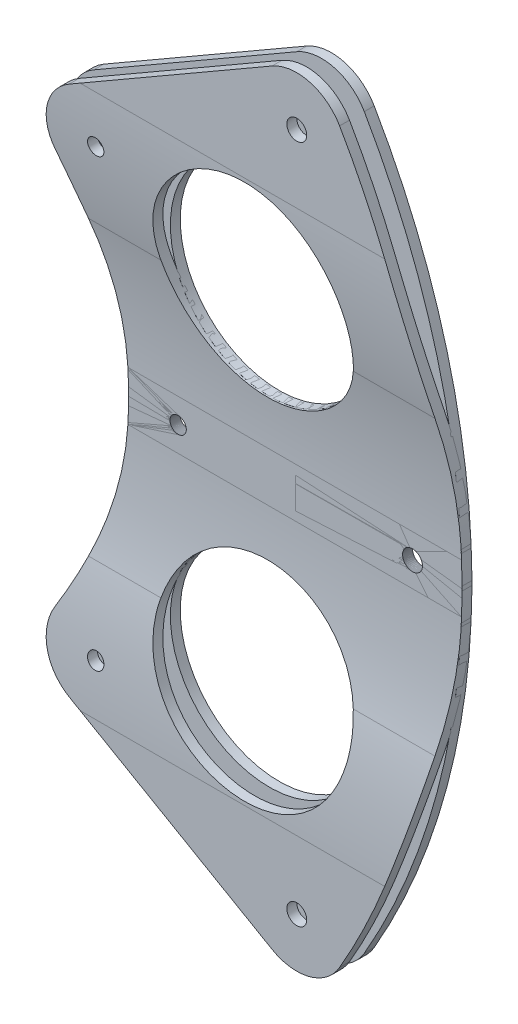
SolidWorks part; units mm, degrees
ref_plane "Front Plane" through (0, 0, 0) normal (0, 0, 1) x (1, 0, 0)
ref_plane "Top Plane" through (0, 0, 0) normal (0, 1, 0) x (1, 0, 0)
ref_plane "Right Plane" through (0, 0, 0) normal (1, 0, 0) x (0, 0, -1)
sketch "Sketch1" plane through (0, 0, 0) normal (0, 0, 1) x (1, 0, 0)
  line L0 (0, 0) -> (174.498, 0) construction
  line L1 (151.1197, 87.249) -> (0, 0) construction
  line L2 (0, 0) -> (151.1197, -87.249) construction
  line L3 (174.498, 0) -> (151.1197, 87.249) construction
  line L4 (174.498, 0) -> (151.1197, -87.249) construction
  line L5 (155.3947, 104.3819) -> (80.9481, 61.4001)
  line L6 (80.9481, -61.4001) -> (155.3947, -104.3819)
  line L7 (144.7697, 98.2475) -> (-25.4, 0) construction
  line L8 (-25.4, 0) -> (144.7697, -98.2475) construction
  circle A0 centre (0, 0) radius 88.9 construction
  circle A1 centre (0, 0) radius 114.3 construction
  circle A2 centre (0, 0) radius 174.498 construction
  circle A3 centre (174.498, 0) radius 2.5527
  circle A4 centre (151.1197, 87.249) radius 2.5527
  circle A5 centre (151.1197, -87.249) radius 2.5527
  circle A6 centre (98.9867, 57.15) radius 2.0955
  circle A8 centre (114.3, 0) radius 2.0955
  circle A9 centre (98.9867, -57.15) radius 2.0955
  arc A10 (155.3947, -104.3819) -> (155.3947, 104.3819) centre (0, 0) ccw
  arc A11 (80.9481, -61.4001) -> (80.9481, 61.4001) centre (0, 0) ccw
  circle A12 centre (0, 0) radius 101.6 construction
  circle A13 centre (0, 0) radius 187.198 construction
  dimension "D1" = 177.8
  dimension "D3" = 348.996
  dimension "D5" = 5.1054
  dimension "D6" = 4.191
  dimension "D4" = 30
  dimension "D2" = 25.4
  dimension "D7" = 12.7
  dimension "D8" = 12.7
extrude "Boss-Extrude1" add sketch "Sketch1" along normal blind 2.54
sketch "Sketch2" plane through (0, 0, 2.54) normal (0, 0, 1) x (1, 0, 0)
  line L2 (114.3, 0) -> (174.498, 0) construction
  line L3 (137.699, -43.4749) -> (137.699, 43.4749) construction
  line L4 (144.399, 0) -> (137.699, 43.4749) construction
  line L5 (137.699, 43.4749) -> (118.1714, 82.891) construction
  line L6 (155.3947, 104.3819) -> (80.9481, 61.4001) construction
  circle A0 centre (0, 0) radius 144.399 construction
  circle A1 centre (114.3, 0) radius 2.0955 construction
  circle A2 centre (137.699, 43.4749) radius 25.4
  circle A3 centre (137.699, -43.4749) radius 25.4
  point P3 (144.399, 0)
  point P16 (137.699, 0)
  dimension "D1" = 50.8
extrude "Cut-Extrude1" cut sketch "Sketch2" against normal through all both and the other way through all
sketch "Sketch3" plane through (0, 0, 0) normal (1, 0, 0) x (0, 0, -1)
  line L0 (-6.35, 87.249) -> (0, 87.249) construction
  line L1 (-6.35, -87.249) -> (0, -87.249) construction
  line L3 (-86.0519, 0) -> (0, 0) construction
  line L4 (0, 6.35) -> (0, -6.35)
  line L5 (-6.35, -104.7115) -> (-6.35, -69.7865)
  line L6 (-6.35, 104.7115) -> (-6.35, 69.7865)
  line L7 (-8.89, -104.7115) -> (-8.89, -69.7865)
  line L8 (-2.54, 6.35) -> (-2.54, -6.35)
  line L9 (-8.89, 104.7115) -> (-8.89, 69.7865)
  line L10 (-8.89, -104.7115) -> (-6.35, -104.7115)
  line L11 (-6.35, 104.7115) -> (-8.89, 104.7115)
  arc A0 (0, -6.35) -> (-3.175, -38.0683) centre (-160.0202, -6.35) cw
  arc A1 (-6.35, -69.7865) -> (-3.175, -38.0683) centre (153.6702, -69.7865) cw
  arc A2 (0, 6.35) -> (-3.175, 38.0683) centre (-160.0202, 6.35) ccw
  arc A3 (-3.175, 38.0683) -> (-6.35, 69.7865) centre (153.6702, 69.7865) cw
  arc A4 (-8.89, -69.7865) -> (-5.6646, -37.5648) centre (153.6702, -69.7865) cw
  arc A5 (-2.54, -6.35) -> (-5.6646, -37.5648) centre (-160.0202, -6.35) cw
  arc A6 (-2.54, 6.35) -> (-5.6646, 37.5648) centre (-160.0202, 6.35) ccw
  arc A7 (-5.6646, 37.5648) -> (-8.89, 69.7865) centre (153.6702, 69.7865) cw
  dimension "D1" = 6.35
  dimension "D2" = 34.925
  dimension "D3" = 12.7
  dimension "D4" = 2.54
extrude "Boss-Extrude2" add sketch "Sketch3" along normal blind 276.098 separate body contours L7 A4 A5 L8 A6 A7 L9 L11 L6 A3 A2 L4 A0 A1 L5 L10
extrude "Cut-Extrude3" cut sketch "Sketch1<2>" along normal blind 276.098 flip side to cut
sketch "Sketch1<2>" plane through (0, 0, 0) normal (0, 0, 1) x (1, 0, 0) same geometry as "Sketch1"
fillet "Fillet1" radius 12.7 4 edges at (155.3947, 104.3819, 1.27) (80.9481, 61.4001, 1.27) (155.3947, -104.3819, 1.27) (80.9481, -61.4001, 1.27)
fillet "Fillet2" radius 12.7 4 edges at (155.3947, -104.3819, 7.62) (80.9481, -61.4001, 7.4018) (80.9481, 61.4001, 7.4018) (155.3947, 104.3819, 7.62)
extrude "Cut-Extrude4" cut sketch "Sketch2<2>" along normal through all both and the other way through all
sketch "Sketch2<2>" plane through (0, 0, 2.54) normal (0, 0, 1) x (1, 0, 0) same geometry as "Sketch2"
